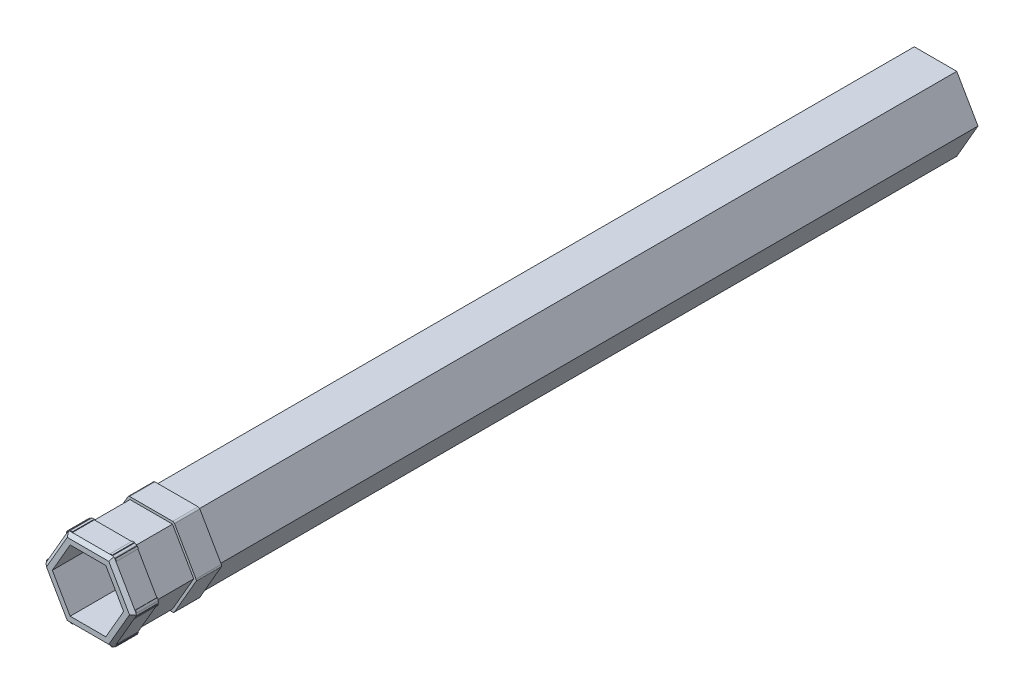
SolidWorks part; units mm, degrees
ref_plane "Front Plane" through (0, 0, 0) normal (0, 0, 1) x (1, 0, 0)
ref_plane "Top Plane" through (0, 0, 0) normal (0, 1, 0) x (1, 0, 0)
ref_plane "Right Plane" through (0, 0, 0) normal (1, 0, 0) x (0, 0, -1)
other "Configuration Table"
sketch "Tube_Full_AF_Profile" plane through (0, 0, 0) normal (0, 0, 1) x (1, 0, 0)
  line L1 (5.3838, 9.325) -> (-5.3838, 9.325)
  line L2 (-5.3838, 9.325) -> (-10.7676, 0)
  line L3 (-10.7676, 0) -> (-5.3838, -9.325)
  line L4 (-5.3838, -9.325) -> (5.3838, -9.325)
  line L5 (5.3838, -9.325) -> (10.7676, 0)
  line L6 (10.7676, 0) -> (5.3838, 9.325)
  point P0 (0, 0)
  point P1 (0, 0)
  dimension "D1" = 18.65
extrude "Tube_Full_AF_Extrusion" add sketch "Tube_Full_AF_Profile" along normal blind 201 contours L1 L2 L3 L4 L5 L6
sketch "Tube_Bore_Profile" plane through (0, 0, 201) normal (0, 0, 1) x (1, 0, 0)
  line L30 (8.4582, 0) -> (4.2291, 7.325)
  line L31 (4.2291, 7.325) -> (-4.2291, 7.325)
  line L32 (-4.2291, 7.325) -> (-8.4582, 0)
  line L33 (-8.4582, 0) -> (-4.2291, -7.325)
  line L34 (-4.2291, -7.325) -> (4.2291, -7.325)
  line L35 (4.2291, -7.325) -> (8.4582, 0)
  line L36 (8.4582, 0) -> (4.2291, 7.325)
  line L37 (4.2291, 7.325) -> (-4.2291, 7.325)
  line L38 (-4.2291, 7.325) -> (-8.4582, 0)
  line L39 (-8.4582, 0) -> (-4.2291, -7.325)
  line L40 (-4.2291, -7.325) -> (4.2291, -7.325)
  line L41 (4.2291, -7.325) -> (8.4582, 0)
extrude "Tube_Bore_Cut" cut sketch "Tube_Bore_Profile" against normal through all and the other way through all
chamfer "T1_Tube_Mouth_Chamfer" [suppressed] distance 0.8 angle 45
chamfer "T1_Bottom_End_Chamfer" [suppressed] distance 0.8 angle 45
sketch "T2_Lower_Relief_Profile" [suppressed] plane through (0, 0, 165) normal (0, 0, 1) x (1, 0, 0)
  line L31 (17.7824, 0) -> (8.8912, 15.4)
  line L32 (8.8912, 15.4) -> (-8.8912, 15.4)
  line L33 (-8.8912, 15.4) -> (-17.7824, 0)
  line L34 (-17.7824, 0) -> (-8.8912, -15.4)
  line L35 (-8.8912, -15.4) -> (8.8912, -15.4)
  line L36 (18.4752, 0) -> (9.2376, 16)
  line L37 (9.2376, 16) -> (-9.2376, 16)
  line L38 (-9.2376, 16) -> (-18.4752, 0)
  line L39 (-18.4752, 0) -> (-9.2376, -16)
  line L40 (-9.2376, -16) -> (9.2376, -16)
  line L41 (9.2376, -16) -> (18.4752, 0)
  line L42 (18.4752, 0) -> (9.2376, 16)
  line L43 (9.2376, 16) -> (-9.2376, 16)
  line L44 (-9.2376, 16) -> (-18.4752, 0)
  line L45 (-18.4752, 0) -> (-9.2376, -16)
  line L46 (-9.2376, -16) -> (9.2376, -16)
  line L47 (9.2376, -16) -> (18.4752, 0)
  line L48 (8.8912, -15.4) -> (17.7824, 0)
  circle A0 centre (0, 0) radius 15.4 construction
  line M19 (18.4752, 0) -> (9.2376, 16)
  line M20 (9.2376, 16) -> (-9.2376, 16)
  line M21 (-9.2376, 16) -> (-18.4752, 0)
  line M22 (-18.4752, 0) -> (-9.2376, -16)
  line M23 (-9.2376, -16) -> (9.2376, -16)
  line M24 (9.2376, -16) -> (18.4752, 0)
  dimension "D2" = 0.6
extrude "T2_Lower_Body_Relief" [suppressed] cut sketch "T2_Lower_Relief_Profile" against normal blind 21 from offset 6 contours L48 L35 L34 L33 L32 L31 M24 M19 M20 M21 M22 M23 offset against normal yes
ref_plane "T2_Stop_Band_Top_Plane" [suppressed] through (0, 0, 198) normal (0, 0, -1) x (-1, 0, 0)
sketch "T2_Upper_Relief_Profile" [suppressed] plane through (0, 0, 198) normal (0, 0, -1) x (-1, 0, 0)
  line L7 (17.7824, 0) -> (8.8912, 15.4)
  line L8 (8.8912, 15.4) -> (-8.8912, 15.4)
  line L9 (-8.8912, 15.4) -> (-17.7824, 0)
  line L10 (-17.7824, 0) -> (-8.8912, -15.4)
  line L11 (-8.8912, -15.4) -> (8.8912, -15.4)
  line L12 (8.8912, -15.4) -> (17.7824, 0)
  line L13 (19.6299, 0) -> (9.815, 17)
  line L14 (9.815, 17) -> (-9.815, 17)
  line L15 (-9.815, 17) -> (-19.6299, 0)
  line L16 (-19.6299, 0) -> (-9.815, -17)
  line L17 (-9.815, -17) -> (9.815, -17)
  line L18 (9.815, -17) -> (19.6299, 0)
  circle A0 centre (0, 0) radius 15.4 construction
  circle A1 centre (0, 0) radius 17 construction
  dimension "D1" = 30.8
  dimension "D2" = 34
extrude "T2_Upper_Body_Relief" [suppressed] cut sketch "T2_Upper_Relief_Profile" against normal blind 132 from offset 198 contours L17 L18 L13 L14 L15 L16 L12 L11 L10 L9 L8 L7
chamfer "T2_Bottom_End_Chamfer" [suppressed] distance 0.8
chamfer "T2_Tube_Mouth_Chamfer" [suppressed] distance 0.8
fillet "T2_Stop_Band_Corner_Fillets" [suppressed] radius 0.5 tangent propagation no
fillet "T2_Guide_Band_Corner_Fillets" [suppressed] radius 0.5
sketch "T2_Guide_Band_Rib_Profile" [suppressed] plane through (0, 16, 0) normal (0, 1, 0) x (1, 0, 0)
  line L5 (0, -159) -> (0, -164.2) construction
  line L10 (-8.9489, -164.2) -> (8.9489, -164.2) construction
  line L11 (-8.9489, -164.2) -> (8.9489, -164.2) construction
  line L13 (-6.25, -159) -> (-5.75, -159)
  line L14 (-6.25, -159) -> (-6.25, -164.2)
  line L15 (-6.25, -164.2) -> (-5.75, -164.2)
  line L16 (-5.75, -159) -> (-5.75, -164.2)
  line L19 (6.25, -164.2) -> (5.75, -164.2)
  line L20 (5.75, -159) -> (5.75, -164.2)
  line L21 (6.25, -159) -> (5.75, -159)
  line L22 (6.25, -159) -> (6.25, -164.2)
  line L27 (8.8912, -159) -> (-8.8912, -159) construction
  line M4 (8.9489, -159) -> (-8.9489, -159)
  line M14 (-8.9489, -164.2) -> (8.9489, -164.2)
  dimension "D1" = 0.5
  dimension "D2" = 5.75
extrude "T2_Guide_Band_Ribs_Master" [suppressed] add sketch "T2_Guide_Band_Rib_Profile" along normal blind 0.15 contours L16 L14 M4 M14 | L22 L20 M4 M14
ref_axis "T2_Tube_Center_Axis" [suppressed] through (0, 0, -18.1285) along (0, 0, 1)
pattern_circular "T2_Guide_Band_Rib_Pattern" [suppressed] count 6 over 360 about axis through (0, 0, -18.1285) along (0, 0, 1) of bodies 115
sketch "T3_Lower_Relief_Profile" plane through (0, 0, 201) normal (0, 0, 1) x (1, 0, 0)
  line L1 (10.0748, 0) -> (5.0374, 8.725)
  line L2 (5.0374, 8.725) -> (-5.0374, 8.725)
  line L3 (-5.0374, 8.725) -> (-10.0748, 0)
  line L4 (-10.0748, 0) -> (-5.0374, -8.725)
  line L5 (-5.0374, -8.725) -> (5.0374, -8.725)
  line L6 (10.7676, 0) -> (5.3838, 9.325)
  line L18 (5.0374, -8.725) -> (10.0748, 0)
  line L62 (10.7676, 0) -> (5.3838, 9.325)
  line L68 (5.3838, 9.325) -> (-5.3838, 9.325)
  line L72 (5.3838, 9.325) -> (-5.3838, 9.325)
  line L74 (-5.3838, 9.325) -> (-10.7676, 0)
  line L76 (-5.3838, 9.325) -> (-10.7676, 0)
  line L78 (-10.7676, 0) -> (-5.3838, -9.325)
  line L79 (-10.7676, 0) -> (-5.3838, -9.325)
  line L80 (-5.3838, -9.325) -> (5.3838, -9.325)
  line L81 (-5.3838, -9.325) -> (5.3838, -9.325)
  line L82 (5.3838, -9.325) -> (10.7676, 0)
  line L83 (5.3838, -9.325) -> (10.7676, 0)
  circle A0 centre (0, 0) radius 8.725 construction
  dimension "D2" = 17.45
extrude "T3_Lower_Body_Relief" [suppressed] cut sketch "T3_Lower_Relief_Profile" against normal blind 15 from offset 6 offset against normal yes
ref_plane "T3_Stop_Band_Top_Plane" [suppressed] through (0, 0, 160) normal (0, 0, 1) x (1, 0, 0)
sketch "T3_Upper_Relief_Profile" [suppressed] plane through (0, 0, 160) normal (0, 0, 1) x (1, 0, 0)
  line L1 (17.7824, 0) -> (8.8912, 15.4)
  line L2 (8.8912, 15.4) -> (-8.8912, 15.4)
  line L3 (-8.8912, 15.4) -> (-17.7824, 0)
  line L4 (-17.7824, 0) -> (-8.8912, -15.4)
  line L5 (-8.8912, -15.4) -> (8.8912, -15.4)
  line L6 (18.4752, 0) -> (9.2376, 16)
  line L7 (9.2376, 16) -> (-9.2376, 16)
  line L8 (-9.2376, 16) -> (-18.4752, 0)
  line L9 (-18.4752, 0) -> (-9.2376, -16)
  line L10 (-9.2376, -16) -> (9.2376, -16)
  line L11 (9.2376, -16) -> (18.4752, 0)
  line L12 (18.4752, 0) -> (9.2376, 16)
  line L13 (9.2376, 16) -> (-9.2376, 16)
  line L14 (-9.2376, 16) -> (-18.4752, 0)
  line L15 (-18.4752, 0) -> (-9.2376, -16)
  line L16 (-9.2376, -16) -> (9.2376, -16)
  line L17 (9.2376, -16) -> (18.4752, 0)
  line L18 (8.8912, -15.4) -> (17.7824, 0)
  circle A0 centre (0, 0) radius 15.4 construction
  dimension "D2" = 17.45
extrude "T3_Upper_Body_Relief" [suppressed] cut sketch "T3_Upper_Relief_Profile" against normal blind 160
chamfer "T3_Bottom_End_Chamfer" [suppressed] distance 0.8 angle 45 tangent propagation no
chamfer "T3_Tube_Mouth_Chamfer" [suppressed] distance 0.8 angle 45 tangent propagation no
fillet "T3_Guide_Band_Corner_Fillets" [suppressed] radius 0.5 tangent propagation no
fillet "T3_Stop_Band_Corner_Fillets" [suppressed] radius 0.5 tangent propagation no
sketch "T3_Guide_Band_Rib_Profile" [suppressed] plane through (0, 16, 0) normal (0, 1, 0) x (1, 0, 0)
  line L0 (0, -181) -> (0, -186.2) construction
  line L1 (8.9489, -181) -> (-8.9489, -181) construction
  line L2 (-8.9489, -186.2) -> (8.9489, -186.2) construction
  line L3 (6.25, -186.2) -> (5.75, -186.2)
  line L4 (-6.25, -181) -> (-5.75, -181)
  line L5 (-6.25, -181) -> (-6.25, -186.2)
  line L6 (-6.25, -186.2) -> (-5.75, -186.2)
  line L7 (-5.75, -181) -> (-5.75, -186.2)
  line L8 (5.75, -181) -> (5.75, -186.2)
  line L9 (6.25, -181) -> (5.75, -181)
  line L10 (6.25, -181) -> (6.25, -186.2)
  dimension "D1" = 0.5
  dimension "D2" = 5.75
extrude "T3_Guide_Band_Ribs_Master" [suppressed] add sketch "T3_Guide_Band_Rib_Profile" along normal blind 0.15
ref_axis " T3_Tube_Center_Axis" [suppressed] through (0, 0, -29.9031) along (0, 0, 1)
pattern_circular " T3_Guide_Band_Rib_Pattern" [suppressed] count 6 over 360 about axis through (0, 0, -29.9031) along (0, 0, 1) of bodies 123
sketch "T4_Lower_Relief_Profile" plane through (0, 0, 201) normal (0, 0, 1) x (1, 0, 0)
  line L1 (10.0748, 0) -> (5.0374, 8.725)
  line L2 (5.0374, 8.725) -> (-5.0374, 8.725)
  line L3 (-5.0374, 8.725) -> (-10.0748, 0)
  line L4 (-10.0748, 0) -> (-5.0374, -8.725)
  line L5 (-5.0374, -8.725) -> (5.0374, -8.725)
  line L6 (10.7676, 0) -> (5.3838, 9.325)
  line L18 (5.0374, -8.725) -> (10.0748, 0)
  line L74 (10.7676, 0) -> (5.3838, 9.325)
  line L80 (5.3838, 9.325) -> (-5.3838, 9.325)
  line L84 (5.3838, 9.325) -> (-5.3838, 9.325)
  line L86 (-5.3838, 9.325) -> (-10.7676, 0)
  line L88 (-5.3838, 9.325) -> (-10.7676, 0)
  line L90 (-10.7676, 0) -> (-5.3838, -9.325)
  line L91 (-10.7676, 0) -> (-5.3838, -9.325)
  line L92 (-5.3838, -9.325) -> (5.3838, -9.325)
  line L93 (-5.3838, -9.325) -> (5.3838, -9.325)
  line L94 (5.3838, -9.325) -> (10.7676, 0)
  line L95 (5.3838, -9.325) -> (10.7676, 0)
  circle A0 centre (0, 0) radius 8.725 construction
  dimension "D2" = 17.45
extrude "T4_Lower_Body_Relief" cut sketch "T4_Lower_Relief_Profile" against normal blind 9 from offset 6 offset against normal yes
ref_plane "T4_Stop_Band_Top_Plane" through (0, 0, 174) normal (0, 0, 1) x (1, 0, 0)
sketch "T4_Upper_Relief_Profile" plane through (0, 0, 174) normal (0, 0, 1) x (1, 0, 0)
  line L1 (10.0748, 0) -> (5.0374, 8.725)
  line L2 (5.0374, 8.725) -> (-5.0374, 8.725)
  line L3 (-5.0374, 8.725) -> (-10.0748, 0)
  line L4 (-10.0748, 0) -> (-5.0374, -8.725)
  line L5 (-5.0374, -8.725) -> (5.0374, -8.725)
  line L6 (10.7676, 0) -> (5.3838, 9.325)
  line L7 (5.3838, 9.325) -> (-5.3838, 9.325)
  line L8 (-5.3838, 9.325) -> (-10.7676, 0)
  line L9 (-10.7676, 0) -> (-5.3838, -9.325)
  line L10 (-5.3838, -9.325) -> (5.3838, -9.325)
  line L11 (5.3838, -9.325) -> (10.7676, 0)
  line L12 (10.7676, 0) -> (5.3838, 9.325)
  line L13 (5.3838, 9.325) -> (-5.3838, 9.325)
  line L14 (-5.3838, 9.325) -> (-10.7676, 0)
  line L15 (-10.7676, 0) -> (-5.3838, -9.325)
  line L16 (-5.3838, -9.325) -> (5.3838, -9.325)
  line L17 (5.3838, -9.325) -> (10.7676, 0)
  line L18 (5.0374, -8.725) -> (10.0748, 0)
  circle A0 centre (0, 0) radius 8.725 construction
  dimension "D2" = 17.45
extrude "T4_Upper_Body_Relief" cut sketch "T4_Upper_Relief_Profile" against normal blind 180 from offset 6 contours L16 L17 L12 L13 L14 L15 L18 L5 L4 L3 L2 L1 region at (7.829, -4.5201, 174)
chamfer "T4_Bottom_End_Chamfer" distance 0.8 angle 45 6 edges at (0, 9.325, 201) (-8.0757, 4.6625, 201) (-8.0757, -4.6625, 201) (0, -9.325, 201) (8.0757, -4.6625, 201) (8.0757, 4.6625, 201) tangent propagation no
chamfer "T4_Tube_Mouth_Chamfer" distance 0.8 angle 45 6 edges at (6.3436, 3.6625, 0) (6.3436, -3.6625, 0) (0, -7.325, 0) (-6.3436, -3.6625, 0) (-6.3436, 3.6625, 0) (0, 7.325, 0)
fillet "T4_Guide_Band_Corner_Fillets" radius 0.5 6 edges at (10.7676, 0, 197.6) (5.3838, -9.325, 197.6) (-5.3838, -9.325, 197.6) (-10.7676, 0, 197.6) (-5.3838, 9.325, 197.6) (5.3838, 9.325, 197.6) tangent propagation no
fillet "T4_Stop_Band_Corner_Fillets" radius 0.5 6 edges at (-5.3838, 9.325, 183) (-10.7676, 0, 183) (-5.3838, -9.325, 183) (5.3838, -9.325, 183) (10.7676, 0, 183) (5.3838, 9.325, 183)
sketch "T4_Guide_Band_Rib_Profile" plane through (0, 9.325, 0) normal (0, 1, 0) x (1, 0, 0)
  line L0 (0, -195) -> (0, -200.2) construction
  line L1 (5.0951, -195) -> (-5.0951, -195) construction
  line L2 (-5.0951, -200.2) -> (5.0951, -200.2) construction
  line L4 (-5, -195) -> (-4.5, -195)
  line L5 (-5, -195) -> (-5, -200.2)
  line L6 (-5, -200.2) -> (-4.5, -200.2)
  line L7 (-4.5, -195) -> (-4.5, -200.2)
  line L8 (5, -200.2) -> (4.5, -200.2)
  line L9 (4.5, -195) -> (4.5, -200.2)
  line L10 (5, -195) -> (4.5, -195)
  line L11 (5, -195) -> (5, -200.2)
  dimension "D1" = 0.5
  dimension "D2" = 4.5
extrude "T4_Guide_Band_Ribs_Master" add sketch "T4_Guide_Band_Rib_Profile" along normal blind 0.15
ref_axis "T4_Tube_Center_Axis" through (0, 0, -78.8763) along (0, 0, 1)
pattern_circular "T4_Guide_Band_Rib_Pattern" count 6 over 360 about axis through (0, 0, -78.8763) along (0, 0, 1) of "T4_Guide_Band_Ribs_Master"
ref_plane "J1_Thread_Boss_Bottom_Plane" [suppressed] through (0, 0, 137) normal (0, 0, 1) x (1, 0, 0)
sketch "J1_Thread_Center_Axis" [suppressed] plane through (0, 0, 0) normal (0, 1, 0) x (1, 0, 0)
  line L0 (0, 3.736) -> (0, -149.1921) construction
sketch "J1_Thread_Boss_Profile" [suppressed] plane through (0, 0, 137) normal (0, 0, 1) x (1, 0, 0)
  line L0 (8.0829, 14) -> (-8.0829, 14) construction
  line L1 (16.1658, 0) -> (8.0829, 14) construction
  line L2 (8.0829, -14) -> (16.1658, 0) construction
  line L3 (-8.0829, -14) -> (8.0829, -14) construction
  line L4 (-16.1658, 0) -> (-8.0829, -14) construction
  line L5 (-8.0829, 14) -> (-16.1658, 0) construction
  line L6 (8.0829, 14) -> (-8.0829, 14)
  line L7 (16.1658, 0) -> (8.0829, 14)
  line L8 (8.0829, -14) -> (16.1658, 0)
  line L9 (-8.0829, -14) -> (8.0829, -14)
  line L10 (-16.1658, 0) -> (-8.0829, -14)
  line L11 (-8.0829, 14) -> (-16.1658, 0)
  circle A0 centre (0, 0) radius 19.05
  dimension "D1" = 38.1
extrude "J1_Thread_Boss_Blank" [suppressed] add sketch "J1_Thread_Boss_Profile" along normal blind 8
chamfer "J1_Thread_Start_Chamfer" [suppressed] distance 0.5 angle 45
sketch "J1_External_Thread_Helix_profile" plane through (0, 0, 201) normal (0, 0, 1) x (1, 0, 0)
  circle A0 centre (0, 0) radius 19.05
  dimension "D1" = 38.1
curve "J1_External_Thread_Helix" [suppressed] pitch 3 height 8 turns 2.6667
ref_plane "J1_Thread_Profile_Plane" [suppressed] through (0, 0, 0) normal (0.8658, 0.4998, 0.0251) x (0.0217, 0.0125, -0.9997)
sketch "J1_External_Thread_Cut_Profile" [suppressed] plane through (0, 0, 0) normal (0.8658, 0.4998, 0.0251) x (0.0217, 0.0125, -0.9997)
  line L0 (0, 0) -> (-151.8685, 0) construction
  line L12 (-145.1607, 17.3101) -> (-145.6463, 18.7186)
  line L13 (-145.1607, 17.3101) -> (-144.1607, 17.293)
  line L15 (-144.1607, 17.293) -> (-143.6273, 18.6841)
  line L16 (-145.6463, 18.7186) -> (-143.6273, 18.6841)
  line L17 (-144.6368, 18.7014) -> (-144.6607, 17.3016) construction
  point P8 (-144.6607, 17.3016)
  point P9 (-144.6368, 18.7014)
  dimension "D1" = 1.4
  dimension "D3" = 20
  dimension "D4" = 2.019
sweep "J1_External_Thread" [suppressed] cut profiles "J1_External_Thread_Cut_Profile" path "J1_External_Thread_Helix"
equation "\"AF\" =18.65"
equation "\"wall\"=2.00mm"
equation "\"clr\"=0.45mm"
equation "\"step\"=4.45mm"
equation "\"tail_h\"=6"
equation "\"stop_h\"=6"
equation "\"relief\"=0.60mm"
equation "\"D1@Tube_Full_AF_Profile\" = \"AF\""
equation "\"D1@Tube_Bore_Profile\" = \"wall\""
equation "\"stop_top\"=33.00mm"
equation "\"D1@T2_Stop_Band_Top_Plane\" = \"stop_top\""
equation "\"D1@T2_Upper_Body_Relief\" = 165 - \"stop_top\""
equation "\"D2@T2_Lower_Relief_Profile\"=\"relief\""
equation "\"D1@T2_Upper_Relief_Profile\"= \"AF\" - 2 * \"relief\""
equation "\"D2@T2_Upper_Relief_Profile\" =  \"AF\" + 2"
equation "\"D1@T2_Lower_Body_Relief\"=\"stop_top\" - \"stop_h\" - \"tail_h\""
equation "\"D19@T2_Upper_Body_Relief\" = 165 + \"stop_top\""
equation "\"D19@T2_Lower_Body_Relief\"= \"tail_h\""
equation "\"D2@T3_Lower_Relief_Profile\"= \"AF\" - 2 * \"relief\""
equation "\"D19@T3_Lower_Body_Relief\" = \"tail_h\""
equation "\"D2@T3_Upper_Relief_Profile\" = \"AF\" - 2 * \"relief\""
equation "\"D2@T4_Lower_Relief_Profile\" = \"AF\" - 2 * \"relief\""
equation "\"D19@T4_Lower_Body_Relief\"=\"tail_h\""
equation "\"D2@T4_Upper_Relief_Profile\" = \"AF\" - 2 * \"relief\""
equation "\"boss_h\"= 8mm"
equation "\"finger_L\"= 12mm"
equation "\"collet_h\"= 14mm"
equation "\"collar_h\"= 22mm"
equation "\"thread_pitch\"= 3mm"
equation "\"thread_depth\"= 1.4mm"
equation "\"cone_half_angle\"= 8deg"
equation "\"lip_clr\"= .3mm"
equation "\"J1_Thread_Major_Dia\"= 38.1mm"
equation "\"J1_Thread_Root_Dia\"= 35.3mm"
equation "\"D1@J1_Thread_Boss_Profile\" = \"J1_Thread_Major_Dia\""
equation "\"D1@J1_Thread_Boss_Blank\" = \"boss_h\""
equation "\"D1@J1_External_Thread_Helix_profile\" = \"J1_Thread_Major_Dia\""
equation "\"D1@J1_External_Thread_Cut_Profile\" = \"thread_depth\""
